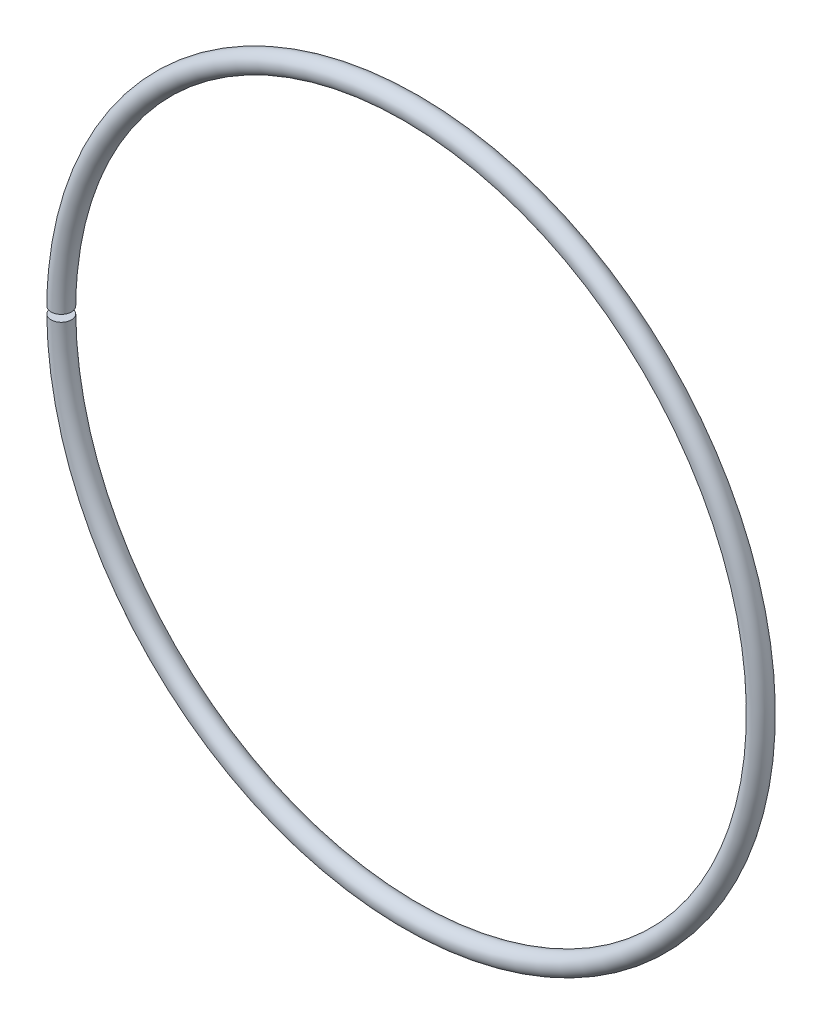
SolidWorks part; units mm, degrees
material "Plain Carbon Steel"
ref_plane "Front Plane" through (0, 0, 0) normal (0, 0, 1) x (1, 0, 0)
ref_plane "Top Plane" through (0, 0, 0) normal (0, 1, 0) x (1, 0, 0)
ref_plane "Right Plane" through (0, 0, 0) normal (1, 0, 0) x (0, 0, -1)
sketch "Sketch1" plane through (0, 0, 0) normal (0, 0, 1) x (1, 0, 0)
  circle A0 centre (0, 0) radius 25.6
  dimension "D1" = 51.2
sketch "Sketch3" plane through (0, 0, 0) normal (0, 1, 0) x (1, 0, 0)
  line L0 (-25.6, 0) -> (25.6, 0) construction
  circle A0 centre (-25.6, 0) radius 0.75
  dimension "D1" = 1.5
  dimension "D2" = 25.6
sweep "Sweep1" add profiles "Sketch3" path "Sketch1"
sketch "Sketch4" plane through (0, 0, 0) normal (0, 0, 1) x (1, 0, 0)
  line L5 (0, 0) -> (0, 0.25)
  line L6 (0, 0.25) -> (-28, 0.25)
  line L7 (-28, 0.25) -> (-28, -0.25)
  line L8 (-28, -0.25) -> (0, -0.25)
  line L9 (0, -0.25) -> (0, 0)
  dimension "D1" = 0.5
  dimension "D2" = 28
extrude "Cut-Extrude1" cut sketch "Sketch4" against normal through all both and the other way through all
ref_axis "Central_Axis" through (0, 0, -7.8601) along (0, 0, 1)
